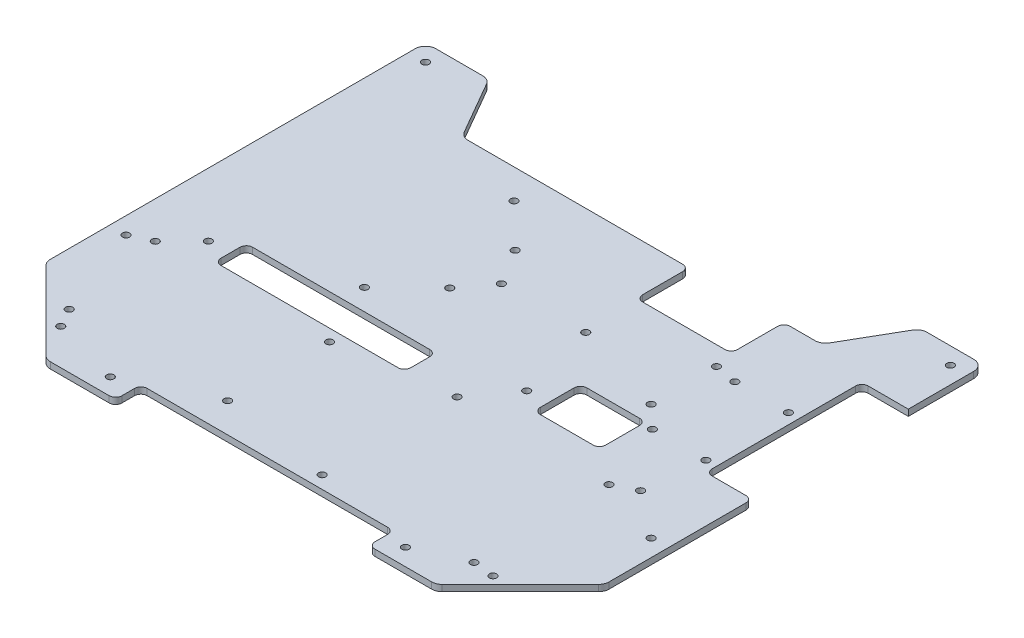
SolidWorks part; units mm, degrees
material "Acier non allié"
ref_plane "Front" through (0, 0, 0) normal (0, 0, 1) x (1, 0, 0)
ref_plane "Top" through (0, 0, 0) normal (0, 1, 0) x (1, 0, 0)
ref_plane "Right" through (0, 0, 0) normal (1, 0, 0) x (0, 0, -1)
sketch "Esquisse1" plane through (0, 0, 0) normal (0, 1, 0) x (1, 0, 0)
  line L0 (0, 0) -> (0, 190) construction
  line L1 (-92.5, 0) -> (92.5, 0)
  line L2 (92.5, 0) -> (132.5, 40)
  line L3 (132.5, 40) -> (132.5, 220)
  line L4 (132.5, 220) -> (102.5, 220)
  line L5 (102.5, 220) -> (85.1795, 190)
  line L6 (85.1795, 190) -> (-85.1795, 190)
  line L7 (-102.5, 220) -> (-85.1795, 190)
  line L8 (-132.5, 220) -> (-102.5, 220)
  line L9 (-132.5, 40) -> (-132.5, 220)
  line L10 (-92.5, 0) -> (-132.5, 40)
  dimension "D1" = 132.5
  dimension "D2" = 220
  dimension "D3" = 60
  dimension "D4" = 30
  dimension "D5" = 40
  dimension "D6" = 40
  dimension "D7" = 30
extrude "Boss.-Extru.1" add sketch "Esquisse1" along normal blind 3
fillet "Congé1" radius 5 10 edges at (92.5, 1.5, 0) (132.5, 1.5, -40) (132.5, 1.5, -220) (102.5, 1.5, -220) (85.1795, 1.5, -190) (-85.1795, 1.5, -190) (-102.5, 1.5, -220) (-132.5, 1.5, -220) (-92.5, 1.5, 0) (-132.5, 1.5, -40)
sketch "Esquisse2" plane through (0, 3, 0) normal (0, 1, 0) x (1, 0, 0)
  line L0 (0, 0) -> (0, 294.1173) construction
  line L2 (-90.4289, 0) -> (90.4289, 0) construction
  circle A0 centre (70, 8) radius 1
  circle A1 centre (124.5, 70) radius 1
  circle A2 centre (124.5, 212) radius 1
  circle A3 centre (-124.5, 212) radius 1
  circle A4 centre (-124.5, 70) radius 1
  circle A5 centre (-70, 8) radius 1
  dimension "D2" = 2
  dimension "D6" = 2
  dimension "D9" = 2
  dimension "D1" = 70
  dimension "D3" = 8
  dimension "D4" = 124.5
  dimension "D5" = 70
  dimension "D7" = 124.5
  dimension "D8" = 212
extrude "Enlèv. mat.-Extru.1" cut sketch "Esquisse2" against normal blind 3
hole_wizard "Dégagement M31" positions "Esquisse3" profile "Esquisse4" hole size "M3" standard "ISO" end condition through all
sketch "Esquisse3" plane through (0, 3, 0) normal (0, 1, 0) x (1, 0, 0)
  point P0 (70, 8)
  point P3 (-70, 8)
  point P6 (-124.5, 70)
  point P9 (-124.5, 212)
  point P12 (124.5, 212)
  point P15 (124.5, 70)
sketch "Esquisse4" plane through (70, 3, -8) normal (1, 0, 0) x (0, 0, 1)
  line L0 (0, 0) -> (0, 3)
  line L1 (0, 3) -> (1.7, 3)
  line L2 (1.7, 3) -> (1.7, 0)
  line L5 (1.7, 0) -> (0, 0)
  line L11 (0, -6.35) -> (0, 107.95) construction
  dimension "Diamètre du perçage jusqu'au prochain" = 3.4
  dimension "Profondeur du perçage jusqu'au prochain" = 3
sketch "Esquisse5" plane through (0, 3, 0) normal (0, 1, 0) x (1, 0, 0)
  line L0 (82.2927, 190) -> (-82.2927, 190) construction
  line L1 (67.5, 190) -> (22.5, 190)
  line L2 (67.5, 190) -> (67.5, 165)
  line L3 (67.5, 165) -> (22.5, 165)
  line L4 (22.5, 190) -> (22.5, 165)
  line L5 (132.5, 42.0711) -> (132.5, 215) construction
  line L6 (132.5, 184) -> (110.5, 184)
  line L7 (132.5, 184) -> (132.5, 110)
  line L8 (132.5, 110) -> (110.5, 110)
  line L9 (110.5, 184) -> (110.5, 110)
  line L10 (127.5, 220) -> (105.3868, 220) construction
  dimension "D1" = 25
  dimension "D2" = 65
  dimension "D3" = 110
  dimension "D4" = 36
  dimension "D5" = 110
  dimension "D6" = 22
extrude "Enlèv. mat.-Extru.2" cut sketch "Esquisse5" against normal through all
fillet "Congé2" radius 3 7 edges at (132.5, 1.5, -110) (110.5, 1.5, -110) (110.5, 1.5, -184) (67.5, 1.5, -190) (67.5, 1.5, -165) (22.5, 1.5, -165) (22.5, 1.5, -190)
sketch "Esquisse6" plane through (0, 3, 0) normal (0, 1, 0) x (1, 0, 0)
  line L0 (110.5, 140.5) -> (-167.6757, 140.5) construction
  line L1 (110.5, 181) -> (110.5, 113) construction
  line L2 (-90.4289, 0) -> (90.4289, 0) construction
  line L3 (110.5, 181) -> (110.5, 113) construction
  circle A0 centre (69.5, 156) radius 1
  circle A1 centre (-26, 156) radius 1
  circle A2 centre (-46.5, 176) radius 1
  circle A3 centre (69.5, 125) radius 1
  circle A4 centre (-26, 125) radius 1
  circle A5 centre (-46.5, 105) radius 1
  dimension "D4" = 2
  dimension "D6" = 2
  dimension "D10" = 2
  dimension "D1" = 140.5
  dimension "D2" = 41
  dimension "D3" = 15.5
  dimension "D5" = 136.5
  dimension "D7" = 15.5
  dimension "D8" = 35.5
  dimension "D9" = 157
extrude "Enlèv. mat.-Extru.3" cut sketch "Esquisse6" against normal through all
hole_wizard "Dégagement M32" positions "Esquisse7" profile "Esquisse8" hole size "M3" standard "ISO"
sketch "Esquisse7" plane through (0, 3, 0) normal (0, 1, 0) x (1, 0, 0)
  point P0 (-46.5, 105)
  point P3 (-26, 125)
  point P6 (-26, 156)
  point P9 (-46.5, 176)
  point P12 (69.5, 156)
  point P15 (69.5, 125)
sketch "Esquisse8" plane through (-46.5, 3, -105) normal (1, 0, 0) x (0, 0, 1)
  line L0 (0, 0) -> (0, 11.0215)
  line L1 (0, 11.0215) -> (1.7, 10)
  line L2 (1.7, 10) -> (1.7, 0)
  line L5 (1.7, 0) -> (0, 0)
  line L10 (0, 11.0215) -> (-1.7, 10) construction
  line L11 (0, -6.35) -> (0, 107.95) construction
  dimension "Diamètre du perçage" = 3.4
  dimension "Profondeur du perçage" = 10
  dimension "Angle de pointe" = 118
sketch "Esquisse9" plane through (0, 3, 0) normal (0, 1, 0) x (1, 0, 0)
  line L0 (132.5, 42.0711) -> (132.5, 107) construction
  line L1 (-90.4289, 0) -> (90.4289, 0) construction
  line L2 (-107.5, 26) -> (-32.37, 26) construction
  line L7 (20.5, 18) -> (20.5, 82) construction
  line L8 (25.5, 165) -> (64.5, 165) construction
  line L9 (24.5, 139) -> (-15.5, 139) construction
  line L10 (110.5, 181) -> (110.5, 113) construction
  line L11 (113.5, 110) -> (129.5, 110) construction
  line L13 (-32.37, 26) -> (-32.37, 74.3362) construction
  line L14 (-32.37, 74.3362) -> (-115, 74.3362) construction
  line L15 (-132.5, 215) -> (-132.5, 42.0711) construction
  circle A0 centre (105.5, 115) radius 1
  circle A3 centre (105.5, 154.12) radius 1
  circle A10 centre (20.5, 82) radius 1
  circle A11 centre (92.5, 82) radius 1
  circle A12 centre (20.5, 18) radius 1
  circle A13 centre (92.5, 18) radius 1
  circle A14 centre (-15.5, 139) radius 1
  circle A15 centre (24.5, 139) radius 1
  circle A16 centre (34.5, 101) radius 1
  circle A17 centre (80.1, 115) radius 1
  circle A18 centre (80.1, 154.12) radius 1
  circle A19 centre (-107.5, 26) radius 1.5
  circle A21 centre (-32.37, 26) radius 1.5
  circle A22 centre (-32.37, 74.3362) radius 1.5
  circle A23 centre (-115, 74.3362) radius 1.5
  dimension "D2" = 2
  dimension "D4" = 2
  dimension "D21" = 2
  dimension "D22" = 2
  dimension "D23" = 2
  dimension "D24" = 2
  dimension "D32" = 2
  dimension "D33" = 2
  dimension "D34" = 2
  dimension "D11" = 2
  dimension "D12" = 2
  dimension "D17" = 3
  dimension "D18" = 3
  dimension "D19" = 3
  dimension "D36" = 3
  dimension "D5" = 27
  dimension "25" = 27
  dimension "D10" = 39.12
  dimension "D25" = 72
  dimension "D26" = 72
  dimension "D27" = 64
  dimension "D28" = 64
  dimension "D30" = 18
  dimension "D31" = 18
  dimension "D37" = 40
  dimension "D39" = 10
  dimension "D7" = 5
  dimension "D8" = 25.4
  dimension "D9" = 25.4
  dimension "D40" = 39.12
  dimension "D38" = 76
  dimension "D6" = 38
  dimension "D35" = 26
  dimension "D14" = 40
  dimension "D13" = 75.13
  dimension "D15" = 82.63
  dimension "D16" = 48.3362
  dimension "D20" = 26
  dimension "D29" = 25
extrude "Enlèv. mat.-Extru.4" cut sketch "Esquisse9" against normal through all
hole_wizard "Dégagement M33" positions "Esquisse10" profile "Esquisse11" hole size "M3" standard "ISO"
sketch "Esquisse10" plane through (0, 3, 0) normal (0, 1, 0) x (1, 0, 0)
  point P3 (105.5, 115)
  point P9 (105.5, 154.12)
  point P14 (80.1, 154.12)
  point P17 (80.1, 115)
sketch "Esquisse11" plane through (105.5, 3, -115) normal (1, 0, 0) x (0, 0, 1)
  line L0 (0, 0) -> (0, 11.0215)
  line L1 (0, 11.0215) -> (1.7, 10)
  line L2 (1.7, 10) -> (1.7, 0)
  line L5 (1.7, 0) -> (0, 0)
  line L10 (0, 11.0215) -> (-1.7, 10) construction
  line L11 (0, -6.35) -> (0, 107.95) construction
  dimension "Diamètre du perçage" = 3.4
  dimension "Profondeur du perçage" = 10
  dimension "Angle de pointe" = 118
sketch "Esquisse12" plane through (0, 3, 0) normal (0, 1, 0) x (1, 0, 0)
  line L2 (-90.4289, 0) -> (90.4289, 0) construction
  line L3 (102.5, 17) -> (-102.5, 17) construction
  line L4 (102.5, 17) -> (102.5, 87) construction
  line L5 (102.5, 87) -> (-102.5, 87) construction
  line L6 (-102.5, 17) -> (-102.5, 87) construction
  line L7 (132.5, 42.0711) -> (132.5, 107) construction
  circle A4 centre (-102.5, 87) radius 1
  circle A5 centre (102.5, 87) radius 1
  circle A6 centre (102.5, 17) radius 1
  circle A7 centre (-102.5, 17) radius 1
  point P6 (102.5, 52)
  dimension "D5" = 2
  dimension "D6" = 2
  dimension "D7" = 2
  dimension "D8" = 2
  dimension "D1" = 70
  dimension "D2" = 205
  dimension "D3" = 17
  dimension "D4" = 30
extrude "Enlèv. mat.-Extru.5" cut sketch "Esquisse12" against normal through all and the other way through all
hole_wizard "Dégagement M34" positions "Esquisse13" profile "Esquisse14" hole size "M3" standard "ISO"
sketch "Esquisse13" plane through (0, 3, 0) normal (0, 1, 0) x (1, 0, 0)
  point P16 (20.5, 18)
  point P19 (92.5, 18)
  point P22 (20.5, 82)
  point P25 (92.5, 82)
  point P29 (34.5, 101)
  point P32 (24.5, 139)
  point P35 (-15.5, 139)
  point P38 (-115, 74.3362)
  point P41 (-32.37, 74.3362)
  point P44 (-107.5, 26)
  point P47 (-32.37, 26)
sketch "Esquisse14" plane through (20.5, 3, -18) normal (1, 0, 0) x (0, 0, 1)
  line L0 (0, 0) -> (0, 11.0215)
  line L1 (0, 11.0215) -> (1.7, 10)
  line L2 (1.7, 10) -> (1.7, 0)
  line L5 (1.7, 0) -> (0, 0)
  line L10 (0, 11.0215) -> (-1.7, 10) construction
  line L11 (0, -6.35) -> (0, 107.95) construction
  dimension "Diamètre du perçage" = 3.4
  dimension "Profondeur du perçage" = 10
  dimension "Angle de pointe" = 118
hole_wizard "Dégagement M35" positions "Esquisse15" profile "Esquisse16" hole size "M3" standard "ISO"
sketch "Esquisse15" plane through (0, 3, 0) normal (0, 1, 0) x (1, 0, 0)
  point P0 (-102.5, 17)
  point P3 (-102.5, 87)
  point P6 (102.5, 87)
  point P9 (102.5, 17)
sketch "Esquisse16" plane through (-102.5, 3, -17) normal (1, 0, 0) x (0, 0, 1)
  line L0 (0, 0) -> (0, 11.0215)
  line L1 (0, 11.0215) -> (1.7, 10)
  line L2 (1.7, 10) -> (1.7, 0)
  line L5 (1.7, 0) -> (0, 0)
  line L10 (0, 11.0215) -> (-1.7, 10) construction
  line L11 (0, -6.35) -> (0, 107.95) construction
  dimension "Diamètre du perçage" = 3.4
  dimension "Profondeur du perçage" = 10
  dimension "Angle de pointe" = 118
sketch "Esquisse17" plane through (0, 3, 0) normal (0, 1, 0) x (1, 0, 0)
  line L0 (-90.4289, 0) -> (90.4289, 0) construction
  line L1 (-92.5, 95) -> (-2.5, 95)
  line L2 (-92.5, 95) -> (-92.5, 80)
  line L3 (-92.5, 80) -> (-2.5, 80)
  line L4 (-2.5, 95) -> (-2.5, 80)
  line L5 (-132.5, 215) -> (-132.5, 42.0711) construction
  line L6 (132.5, 42.0711) -> (132.5, 107) construction
  line L7 (44.5, 116.5) -> (75.5, 116.5)
  line L8 (44.5, 116.5) -> (44.5, 94.5)
  line L9 (44.5, 94.5) -> (75.5, 94.5)
  line L10 (75.5, 116.5) -> (75.5, 94.5)
  line L11 (82.2927, 190) -> (70.5, 190) construction
  line L13 (-59.5, 12) -> (60.5, 12)
  line L14 (-59.5, 12) -> (-59.5, 0)
  line L15 (-59.5, 0) -> (60.5, 0)
  line L16 (60.5, 12) -> (60.5, 0)
  dimension "D1" = 90
  dimension "D2" = 15
  dimension "D3" = 80
  dimension "D4" = 40
  dimension "D5" = 31
  dimension "D6" = 22
  dimension "D7" = 57
  dimension "D8" = 73.5
  dimension "D9" = 12
  dimension "D11" = 120
  dimension "D12" = 72
extrude "Enlèv. mat.-Extru.6" cut sketch "Esquisse17" against normal up to surface (3 mm away) up to face at (-102.5, 0, -15.3)
fillet "Congé3" radius 3 12 edges at (60.5, 1.5, 0) (60.5, 1.5, -12) (-59.5, 1.5, -12) (-59.5, 1.5, 0) (44.5, 1.5, -116.5) (75.5, 1.5, -116.5) (75.5, 1.5, -94.5) (44.5, 1.5, -94.5) (-92.5, 1.5, -80) (-2.5, 1.5, -80) (-2.5, 1.5, -95) (-92.5, 1.5, -95)
equation "\"WIDTH\"= 300mm'Total width of the robot"
equation "\"LENGTH\"= 220mm'Total length of the robot"
equation "\"CUT_DEPTH\"= 45mm'Depth of the cut on the edges of the plate"
equation "\"Plate_th\"= 3mm'Thickness of the plate"
equation "\"D1\"= \"Plate_th\""
equation "\"D5@Esquisse9\"=\"25@Esquisse9\""
